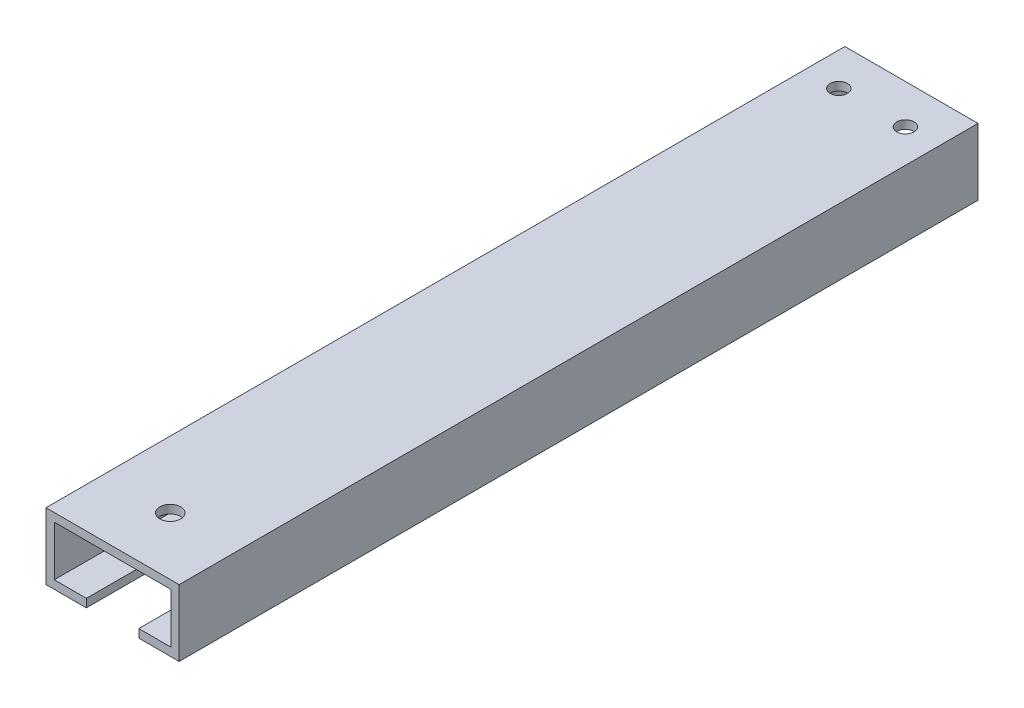
SolidWorks part; units mm, degrees
material "6061 Alloy"
ref_plane "Front Plane" through (0, 0, 0) normal (0, 0, 1) x (1, 0, 0)
ref_plane "Top Plane" through (0, 0, 0) normal (0, 1, 0) x (1, 0, 0)
ref_plane "Right Plane" through (0, 0, 0) normal (1, 0, 0) x (0, 0, -1)
sketch "Sketch1" plane through (0, 0, 0) normal (0, 0, 1) x (1, 0, 0)
  line L0 (-11.1125, 4.7625) -> (11.1125, 4.7625)
  line L2 (-12.7, 6.35) -> (12.7, 6.35)
  line L3 (-12.7, 6.35) -> (-12.7, -6.35)
  line L4 (-12.7, -6.35) -> (12.7, -6.35)
  line L5 (12.7, 6.35) -> (12.7, -6.35)
  line L10 (11.1125, 4.7625) -> (11.1125, -4.7625)
  line L11 (-11.1125, -4.7625) -> (11.1125, -4.7625)
  line L12 (-11.1125, 4.7625) -> (-11.1125, -4.7625)
  point P12 (0, 6.35)
  point P14 (12.7, 0)
  dimension "Wall Thickness" = 1.5875
  dimension "Outside Width" = 25.4
  dimension "Outside Height" = 12.7
  dimension "Inside Height" = 9.525
  dimension "Inside Width" = 22.225
sketch "Sketch2" plane through (0, 0, 0) normal (1, 0, 0) x (0, 0, -1)
  line L0 (304.8, 0) -> (-304.8, 0)
  point P4 (0, 0)
  point P7 (-304.8, 0)
  point P10 (304.8, 0)
  dimension "Length" = 609.6
sketch "Sketch3" plane through (0, 0, 0) normal (0, 0, 1) x (1, 0, 0)
  line L21 (12.7, 6.35) -> (-12.7, 6.35)
  line L22 (12.7, -6.35) -> (12.7, 6.35)
  line L23 (-12.7, -6.35) -> (12.7, -6.35)
  line L24 (-12.7, 6.35) -> (-12.7, -6.35)
  line L25 (12.7, 6.35) -> (-12.7, 6.35)
  line L26 (12.7, -6.35) -> (12.7, 6.35)
  line L27 (-12.7, -6.35) -> (12.7, -6.35)
  line L28 (-12.7, 6.35) -> (-12.7, -6.35)
  line L29 (11.1125, 4.7625) -> (-11.1125, 4.7625)
  line L30 (11.1125, -4.7625) -> (11.1125, 4.7625)
  line L31 (-11.1125, -4.7625) -> (11.1125, -4.7625)
  line L32 (-11.1125, 4.7625) -> (-11.1125, -4.7625)
  line L33 (11.1125, 4.7625) -> (-11.1125, 4.7625)
  line L34 (11.1125, -4.7625) -> (11.1125, 4.7625)
  line L35 (-11.1125, -4.7625) -> (11.1125, -4.7625)
  line L36 (-11.1125, 4.7625) -> (-11.1125, -4.7625)
  dimension "D1" = 0
  dimension "D2" = 0
extrude "Boss-Extrude1" add sketch "Sketch3" along normal blind 152.4
sketch "Drawing Reference" plane through (0, 0, 0) normal (1, 0, 0) x (0, 0, -1)
  line L0 (-304.8, 0) -> (304.8, 0) construction
  line L1 (-76.2, -6.35) -> (-76.2, 6.35) construction
  line L2 (-152.4, -6.35) -> (0, -6.35) construction
  line L5 (-152.4, 6.35) -> (0, 6.35) construction
  point P7 (-286.512, 0)
  point P8 (134.112, 0)
  dimension "D1" = 18.288
sketch "Sketch4" plane through (0, 6.35, 0) normal (0, 1, 0) x (1, 0, 0)
  line L0 (-12.7, -152.4) -> (-12.7, 0) construction
  line L1 (12.7, -152.4) -> (-12.7, -152.4) construction
  circle A0 centre (0, -141.4) radius 2
  dimension "D1" = 4
  dimension "D2" = 11
  dimension "D3" = 12.7
extrude "Cut-Extrude1" cut sketch "Sketch4" against normal up to surface (1.5875 mm away) up to face at (0, 4.7625, 76.2)
sketch "Sketch5" plane through (0, -6.35, 0) normal (0, -1, 0) x (1, 0, 0)
  circle A1 centre (-8, 141.4) radius 1.5004
  circle A2 centre (0, 149.4) radius 1.5004
  circle A3 centre (8, 141.4) radius 1.5004
  point P12 (0, 141.4)
extrude "Cut-Extrude2" cut sketch "Sketch5" against normal up to surface (1.5875 mm away) up to face at (0, -4.7625, 76.2)
sketch "Sketch6" plane through (0, -6.35, 0) normal (0, -1, 0) x (1, 0, 0)
  line L0 (-5, 152.4) -> (-5, 136.4)
  line L1 (-12.7, 152.4) -> (12.7, 152.4) construction
  line L2 (-5, 136.4) -> (5, 136.4)
  line L3 (5, 136.4) -> (5, 152.4)
  line L4 (-8, 141.4) -> (8, 141.4) construction
  line L5 (0, 149.4) -> (0, 127.1732) construction
  circle A0 centre (-8, 141.4) radius 1.5004 construction
  circle A1 centre (8, 141.4) radius 1.5004 construction
  circle A3 centre (0, 141.4) radius 5 construction
  point P18 (0, 141.4)
  dimension "D1" = 10
extrude "Cut-Extrude3" cut sketch "Sketch6" against normal blind 2.54 and the other way through all
ref_plane "Plane1" through (0, -6.35, 0) normal (0, -1, 0) x (-1, 0, 0)
sketch "Sketch7" plane through (0, -6.35, 0) normal (0, -1, 0) x (-1, 0, 0)
  line L0 (-12.7, -152.4) -> (-12.7, 0) construction
  line L1 (12.7, 0) -> (-12.7, 0) construction
  point P0 (-6.35, -7.5)
  point P1 (6.35, -7.5)
  dimension "D1" = 12.7
  dimension "D2" = 6.35
  dimension "D3" = 7.5
hole_wizard "M4x0.7 Tapped Hole1" positions "Sketch8" profile "Sketch9" tap size "M4x0.7" standard "ANSI Metric" end condition through all
sketch "Sketch8" plane through (0, -6.35, 0) normal (0, -1, 0) x (-1, 0, 0)
  point P0 (-6.35, -7.5)
  point P3 (6.35, -7.5)
sketch "Sketch9" plane through (6.35, -6.35, 7.5) normal (1, 0, 0) x (0, 0, -1)
  line L0 (0, 0) -> (0, 12.7)
  line L1 (0, 12.7) -> (1.65, 12.7)
  line L2 (1.65, 12.7) -> (1.65, 0)
  line L5 (1.65, 0) -> (0, 0)
  line L11 (0, -6.35) -> (0, 107.95) construction
  dimension "Thru Tap Drill Dia." = 3.3
  dimension "Thru Tap Drill Depth" = 12.7
equation "\"D1@Drawing Reference\"=\"Outside Width@Sketch1\" * 0.72"
